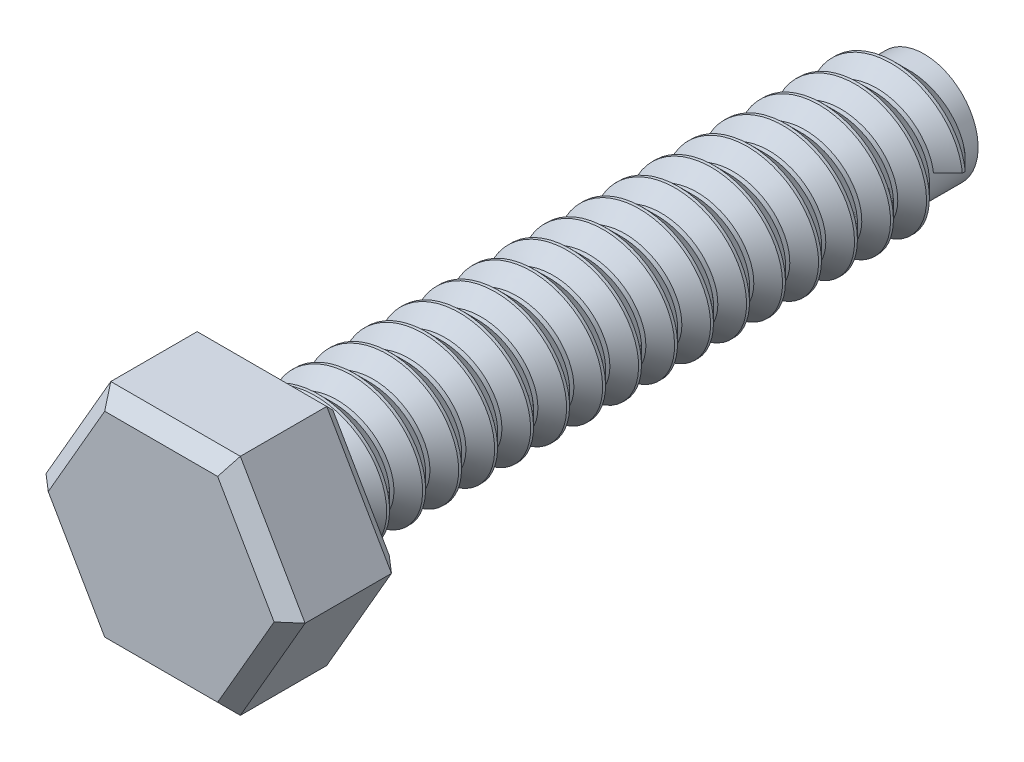
SolidWorks part; units mm, degrees
ref_plane "前视基准面" through (0, 0, 0) normal (0, 0, 1) x (1, 0, 0)
ref_plane "上视基准面" through (0, 0, 0) normal (0, 1, 0) x (1, 0, 0)
ref_plane "右视基准面" through (0, 0, 0) normal (1, 0, 0) x (0, 0, -1)
sketch "草图1" plane through (0, 0, 0) normal (0, 0, 1) x (1, 0, 0)
  line L1 (9, 0) -> (4.5, 7.7942)
  line L2 (4.5, 7.7942) -> (-4.5, 7.7942)
  line L3 (-4.5, 7.7942) -> (-9, 0)
  line L4 (-9, 0) -> (-4.5, -7.7942)
  line L5 (-4.5, -7.7942) -> (4.5, -7.7942)
  line L6 (4.5, -7.7942) -> (9, 0)
  circle A0 centre (0, 0) radius 9
  circle A1 centre (0, 0) radius 7.7942 construction
  dimension "D1" = 18
extrude "凸台-拉伸1" add sketch "草图1" along normal blind 8 contours L2 L3 L4 L5 L6 L1
sketch "草图6" plane through (0, 0, 0) normal (0, 0, -1) x (-1, 0, 0)
  circle A1 centre (0, 0) radius 3.75
  dimension "D1" = 7.5
extrude "凸台-拉伸2" add sketch "草图6" along normal blind 45
ref_plane "基准面1" through (0, 0, -1.75) normal (0, 0, -1) x (-1, 0, 0)
sketch "草图7" plane through (0, 0, -1.75) normal (0, 0, -1) x (-1, 0, 0)
  circle A1 centre (0, 0) radius 3.75
  circle A2 centre (0, 0) radius 3.75 construction
curve "螺旋线/涡状线2" pitch 2.5 height 41.25 radius 3.75 centre (0, 0, -1.75) axis (0, 0, -1) start towards (-1, 0, 0)
sketch "草图8" plane through (0, 0, 0) normal (0, 1, 0) x (1, 0, 0)
  line L0 (-3.75, 2.85) -> (-3.75, 0.65)
  line L1 (-3.75, 0.65) -> (-4.75, 1.65)
  line L2 (-4.75, 1.65) -> (-4.75, 1.85)
  line L3 (-4.75, 1.85) -> (-3.75, 2.85)
  point P7 (-3.75, 1.75)
  dimension "D1" = 1
  dimension "D2" = 2.2
  dimension "D3" = 45
  dimension "D4" = 45
sweep "扫描1" add profiles "草图8" path "螺旋线/涡状线2"
chamfer "倒角1" distance 1 angle 45 12 edges at (0, -7.7942, 0) (6.75, -3.8971, 0) (-6.75, -3.8971, 0) (-6.75, 3.8971, 0) (0, 7.7942, 0) (6.75, 3.8971, 0) (-6.75, 3.8971, 8) (-6.75, -3.8971, 8) (0, -7.7942, 8) (6.75, -3.8971, 8) (6.75, 3.8971, 8) (0, 7.7942, 8)
